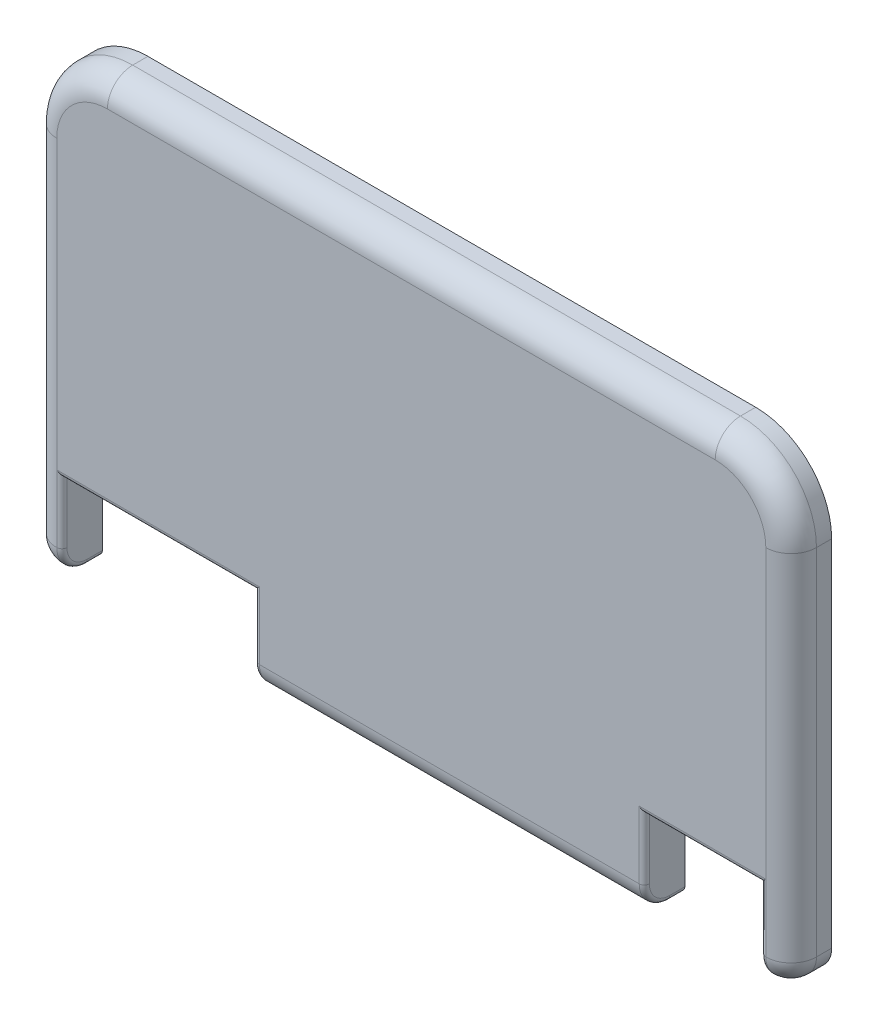
SolidWorks part; units mm, degrees
ref_plane "Alzado" through (0, 0, 0) normal (0, 0, 1) x (1, 0, 0)
ref_plane "Planta" through (0, 0, 0) normal (0, 1, 0) x (1, 0, 0)
ref_plane "Vista lateral" through (0, 0, 0) normal (1, 0, 0) x (0, 0, -1)
sketch "Croquis1" plane through (0, 0, 0) normal (0, 0, 1) x (1, 0, 0)
  line L12 (69, -45) -> (70, -45)
  line L13 (75, -40) -> (75, 30)
  line L14 (60, 45) -> (-60, 45)
  line L15 (-75, 30) -> (-75, -40)
  line L16 (-70, -45) -> (-69, -45)
  line L17 (-69, -45) -> (-69, -27.7)
  line L18 (-69, -27.7) -> (-31, -27.7)
  line L19 (-31, -27.7) -> (-31, -45)
  line L20 (-31, -45) -> (46, -45)
  line L21 (46, -45) -> (46, -27.7)
  line L22 (46, -27.7) -> (69, -27.7)
  line L23 (69, -27.7) -> (69, -45)
  line L24 (69, -45) -> (70, -45)
  line L25 (75, -40) -> (75, 30)
  line L26 (60, 45) -> (-60, 45)
  line L27 (-75, 30) -> (-75, -40)
  line L28 (-70, -45) -> (-69, -45)
  line L29 (-69, -45) -> (-69, -27.7)
  line L30 (-69, -27.7) -> (-31, -27.7)
  line L31 (-31, -27.7) -> (-31, -45)
  line L32 (-31, -45) -> (46, -45)
  line L33 (46, -45) -> (46, -27.7)
  line L34 (46, -27.7) -> (69, -27.7)
  line L35 (69, -27.7) -> (69, -45)
  arc A4 (70, -45) -> (75, -40) centre (70, -40) ccw
  arc A5 (75, 30) -> (60, 45) centre (60, 30) ccw
  arc A6 (-60, 45) -> (-75, 30) centre (-60, 30) ccw
  arc A7 (-75, -40) -> (-70, -45) centre (-70, -40) ccw
  arc A8 (70, -45) -> (75, -40) centre (70, -40) ccw
  arc A9 (75, 30) -> (60, 45) centre (60, 30) ccw
  arc A10 (-60, 45) -> (-75, 30) centre (-60, 30) ccw
  arc A11 (-75, -40) -> (-70, -45) centre (-70, -40) ccw
  dimension "D1" = 0
extrude "Saliente-Extruir1" add sketch "Croquis1" along normal blind 8
fillet "Redondeo1" radius 5 1 edges at (-75, -5, 8) type face fillet first side face at (1.875, -19.1661, 8) second side face at (-75, -5, 4)
fillet "Redondeo2" radius 5 1 edges at (7.5, -45, 8) type face fillet first side face at (2.1429, -15.4756, 8) second side face at (7.5, -45, 4)
fillet "Redondeo3" radius 1 14 edges at (69, -45, 1.5) (69, -43.5355, 6.5355) (-69, -45, 1.5) (-69, -43.5355, 6.5355) (69, -33.85, 8) (57.5, -27.7, 8) (-69, -33.85, 8) (-50, -27.7, 8) (-31, -45, 1.5) (-31, -43.5355, 6.5355) (46, -45, 1.5) (46, -43.5355, 6.5355) (-31, -33.85, 8) (46, -33.85, 8)
sketch "Croquis2" plane through (0, 0, 0) normal (0, 0, -1) x (-1, 0, 0)
  circle A0 centre (67, -19.7) radius 3.6
  circle A1 centre (64.0711, 34.0711) radius 3.6
  circle A2 centre (-67, -19.7) radius 3.6
  circle A3 centre (-64.0711, 34.0711) radius 3.6
  dimension "D1" = 7.2
extrude "Cortar-Extruir1" cut sketch "Croquis2" against normal blind 2
